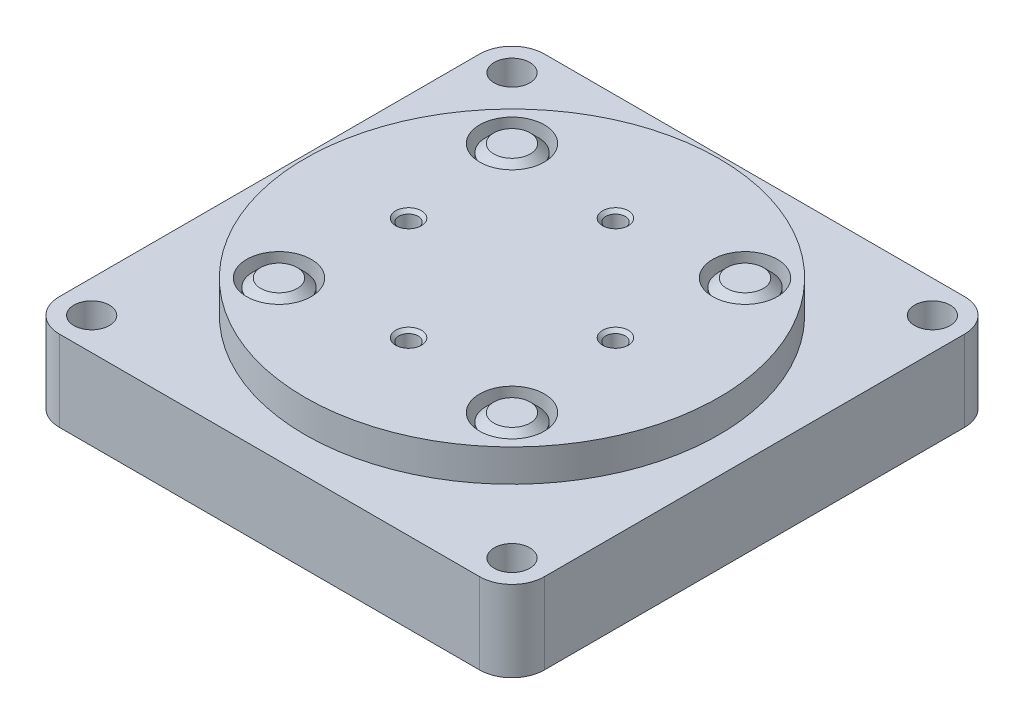
SolidWorks part; units mm, degrees
ref_plane "Front Plane" through (0, 0, 0) normal (0, 0, 1) x (1, 0, 0)
ref_plane "Top Plane" through (0, 0, 0) normal (0, 1, 0) x (1, 0, 0)
ref_plane "Right Plane" through (0, 0, 0) normal (1, 0, 0) x (0, 0, -1)
sketch "Sketch1" plane through (0, 0, 0) normal (0, 1, 0) x (1, 0, 0)
  line L1 (-38.1, -38.1) -> (38.1, -38.1)
  line L2 (-38.1, -38.1) -> (-38.1, 38.1)
  line L3 (-38.1, 38.1) -> (38.1, 38.1)
  line L4 (38.1, -38.1) -> (38.1, 38.1)
  line L5 (-38.1, -38.1) -> (38.1, 38.1) construction
  line L6 (-38.1, 38.1) -> (38.1, -38.1) construction
  point P0 (0, 0)
  dimension "D1" = 76.2
  dimension "D2" = 76.2
extrude "Boss-Extrude1" add sketch "Sketch1" along normal blind 12.7
sketch "Sketch2" plane through (0, 12.7, 0) normal (0, 1, 0) x (1, 0, 0)
  line L0 (38.1, -38.1) -> (38.1, 38.1) construction
  line L1 (0, 0) -> (38.1, 38.1) construction
  circle A0 centre (0, 0) radius 38.1 construction
  circle A1 centre (0, 0) radius 32.512
  circle A2 centre (33.02, 33.02) radius 2.794
  circle A3 centre (33.02, -33.02) radius 2.794
  circle A4 centre (-33.02, -33.02) radius 2.794
  circle A5 centre (-33.02, 33.02) radius 2.794
  point P20 (0, 0)
  dimension "D2" = 5.588
  dimension "D3" = 5.08
  dimension "D4" = 4
  dimension "D1" = 5.588
extrude "Cut-Extrude1" cut sketch "Sketch2" against normal through all contours A3 | A2 | A4 | A5
extrude "Boss-Extrude2" add sketch "Sketch2<3>" along normal blind 5.08 contours A1
sketch "Sketch2<3>" plane through (0, 12.7, 0) normal (0, 1, 0) x (1, 0, 0) same geometry as "Sketch2"
fillet "Fillet1" radius 5.08 4 edges at (-38.1, 6.35, 38.1) (38.1, 6.35, 38.1) (38.1, 6.35, -38.1) (-38.1, 6.35, -38.1)
sketch "Sketch3" plane through (0, 17.78, 0) normal (0, 1, 0) x (1, 0, 0)
  line L0 (0, 0) -> (36.6121, 36.6121) construction
  line L1 (0, 0) -> (0, 32.512) construction
  arc A0 (38.1, 33.02) -> (33.02, 38.1) centre (33.02, 33.02) ccw construction
  circle A1 centre (18.3061, 18.3061) radius 5.08
  circle A2 centre (18.3061, 18.3061) radius 4.1275
  circle A3 centre (18.3061, -18.3061) radius 4.1275
  circle A4 centre (18.3061, -18.3061) radius 5.08
  circle A5 centre (-18.3061, -18.3061) radius 4.1275
  circle A6 centre (-18.3061, -18.3061) radius 5.08
  circle A7 centre (-18.3061, 18.3061) radius 4.1275
  circle A8 centre (-18.3061, 18.3061) radius 5.08
  circle A9 centre (0, 0) radius 32.512 construction
  circle A10 centre (0, 16.256) radius 1.524
  circle A11 centre (16.256, 0) radius 1.524
  circle A12 centre (0, -16.256) radius 1.524
  circle A13 centre (-16.256, 0) radius 1.524
  point P21 (0, 0)
  point P25 (7.7646, -16.1681)
  point P34 (0, 0)
  dimension "D1" = 10.16
  dimension "D2" = 8.255
  dimension "D4" = 3.048
  dimension "D3" = 4
  dimension "D5" = 4
extrude "Cut-Extrude2" cut sketch "Sketch3" against normal blind 7.62
chamfer "Chamfer1" distance 1.27 4 edges at (18.3061, 17.78, 22.4336) (18.3061, 17.78, -14.1786) (-18.3061, 17.78, -14.1786) (-18.3061, 17.78, 22.4336)
chamfer "Chamfer2" distance 0.508 4 edges at (0, 17.78, 17.78) (16.256, 17.78, 1.524) (0, 17.78, -14.732) (-16.256, 17.78, 1.524)
